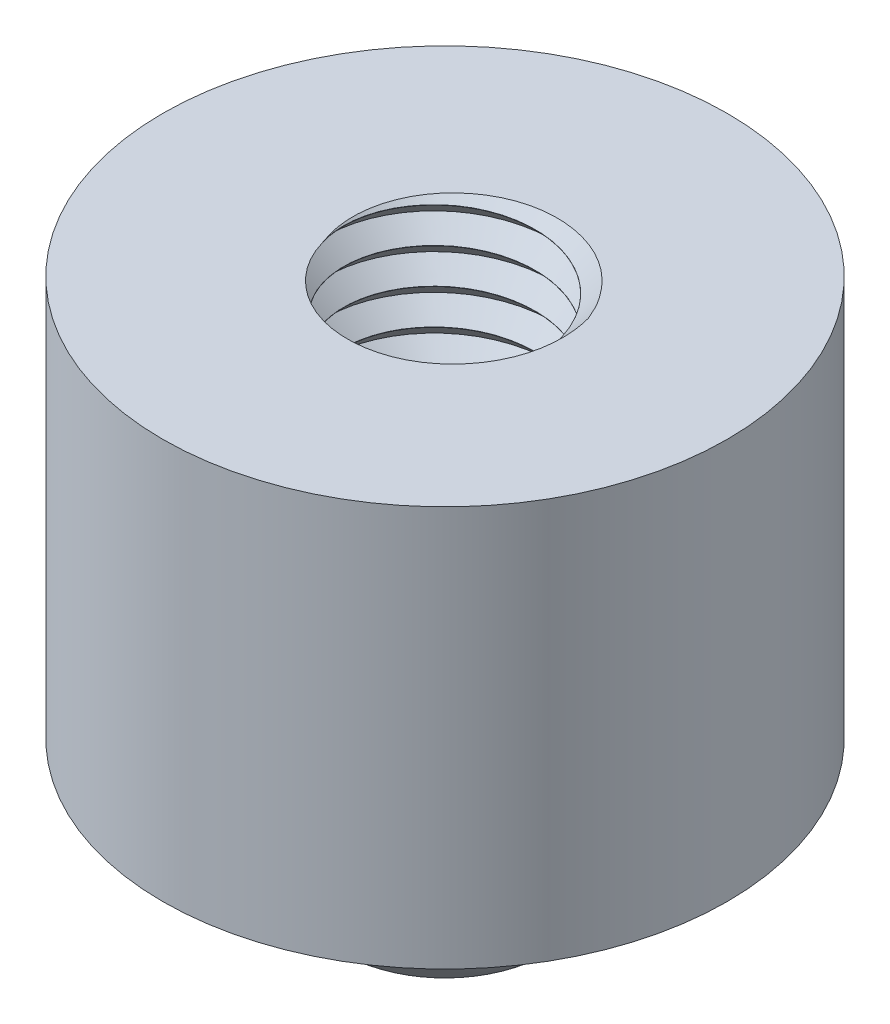
SolidWorks part; units mm, degrees
other "Markup1"
sketch "Sketch7" plane through (8, -40.1821, 8) normal (0.788, -0.5726, 0.226) x (0.2068, -0.0996, -0.9733)
other "Markup2"
sketch "Sketch8" plane through (10, -42.1821, -10) normal (0.2153, -0.7341, -0.6439) x (-0.8854, 0.1314, -0.4459)
material "7075-T6，板材(SS)"
ref_plane "前视基准面" through (0, 0, 0) normal (0, 0, 1) x (1, 0, 0)
ref_plane "上视基准面" through (0, 0, 0) normal (0, 1, 0) x (1, 0, 0)
ref_plane "右视基准面" through (0, 0, 0) normal (1, 0, 0) x (0, 0, -1)
sketch "草图1" plane through (0, 0, 0) normal (0, 0, 1) x (1, 0, 0)
  line L0 (0, 16.878) -> (0, -16.878) construction
  line L1 (0, 0) -> (3.4, 0) construction
  line L3 (3.4, 0) -> (10, 0)
  line L4 (3.4, 0) -> (3.4, -11)
  line L5 (3.4, -11) -> (10, -11)
  line L6 (10, 0) -> (10, -11)
  point P4 (0, 0)
  dimension "D1" = 3.4
  dimension "D2" = 10
  dimension "D3" = 11
revolve "旋转1" add sketch "草图1" angle 360 about L0
sketch "草图2" plane through (0, -11, 0) normal (0, -1, 0) x (1, 0, 0)
  circle A0 centre (0, 0) radius 3.4 construction
  circle A1 centre (0, 0) radius 3.4
curve "螺旋线/涡状线1" pitch 1.25 height 12.8125 radius 3.4 centre (0, -11, 0) axis (0, 1, 0) start towards (0, 0, -1)
sketch "草图3" plane through (0, 0, 0) normal (1, 0, 0) x (0, 0, -1)
  line L0 (3.4, -11.62) -> (3.4, -10.38)
  line L1 (3.4, -10.38) -> (4.025, -11)
  line L2 (-10, -11) -> (10, -11) construction
  line L3 (0, 0) -> (0, -13.2999) construction
  line L4 (-10, -11) -> (10, -11) construction
  line L5 (3.4, -11.62) -> (4.025, -11)
  spline S0 degree 3 poles (-1995.5188, 50.9214) (-241.4894, -14.1354) (17.2925, -12.3735) (2.4668, -10.8438) (1.335, -10.7656) (0, -10.6875) (-1.335, -10.6094) (-2.4668, -10.5313) (-3.223, -10.4531) (-3.4885, -10.375) (-3.223, -10.2969) (-2.4668, -10.2188) (-0.9577, -10.1146) (0.9577, -10.0104) (2.4668, -9.9063) (3.223, -9.8281) (3.4885, -9.75) (3.223, -9.6719) (2.4668, -9.5938) (0.9577, -9.4896) (-0.9577, -9.3854) (-2.4668, -9.2812) (-3.223, -9.2031) (-3.4885, -9.125) (-3.223, -9.0469) (-2.4668, -8.9687) (-0.9577, -8.8646) (0.9577, -8.7604) (2.4668, -8.6562) (3.223, -8.5781) (3.4885, -8.5) (3.223, -8.4219) (2.4668, -8.3437) (0.9577, -8.2396) (-0.9577, -8.1354) (-2.4668, -8.0312) (-3.223, -7.9531) (-3.4885, -7.875) (-3.223, -7.7969) (-2.4668, -7.7187) (-0.9577, -7.6146) (0.9577, -7.5104) (2.4668, -7.4062) (3.223, -7.3281) (3.4885, -7.25) (3.223, -7.1719) (2.4668, -7.0937) (0.9577, -6.9896) (-0.9577, -6.8854) (-2.4668, -6.7812) (-3.223, -6.7031) (-3.4885, -6.625) (-3.223, -6.5469) (-2.4668, -6.4687) (-0.9577, -6.3646) (0.9577, -6.2604) (2.4668, -6.1562) (3.223, -6.0781) (3.4885, -6) (3.223, -5.9219) (2.4668, -5.8437) (0.9577, -5.7396) (-0.9577, -5.6354) (-2.4668, -5.5312) (-3.223, -5.4531) (-3.4885, -5.375) (-3.223, -5.2969) (-2.4668, -5.2187) (-0.9577, -5.1146) (0.9577, -5.0104) (2.4668, -4.9062) (3.223, -4.8281) (3.4885, -4.75) (3.223, -4.6719) (2.4668, -4.5937) (0.9577, -4.4896) (-0.9577, -4.3854) (-2.4668, -4.2812) (-3.223, -4.2031) (-3.4885, -4.125) (-3.223, -4.0469) (-2.4668, -3.9687) (-0.9577, -3.8646) (0.9577, -3.7604) (2.4668, -3.6562) (3.223, -3.5781) (3.4885, -3.5) (3.223, -3.4219) (2.4668, -3.3437) (0.9577, -3.2396) (-0.9577, -3.1354) (-2.4668, -3.0312) (-3.223, -2.9531) (-3.4885, -2.875) (-3.223, -2.7969) (-2.4668, -2.7187) (-0.9577, -2.6146) (0.9577, -2.5104) (2.4668, -2.4062) (3.223, -2.3281) (3.4885, -2.25) (3.223, -2.1719) (2.4668, -2.0937) (0.9577, -1.9896) (-0.9577, -1.8854) (-2.4668, -1.7812) (-3.223, -1.7031) (-3.4885, -1.625) (-3.223, -1.5469) (-2.4668, -1.4687) (-0.9577, -1.3646) (0.9577, -1.2604) (2.4668, -1.1562) (3.223, -1.0781) (3.4885, -1) (3.223, -0.9219) (2.4668, -0.8437) (0.9577, -0.7396) (-0.9577, -0.6354) (-2.4668, -0.5312) (-3.223, -0.4531) (-3.4885, -0.375) (-3.223, -0.2969) (-2.4668, -0.2187) (-0.9577, -0.1146) (0.9577, -0.0104) (2.4668, 0.0938) (3.223, 0.1719) (3.4885, 0.25) (3.223, 0.3281) (2.4668, 0.4063) (0.9577, 0.5104) (-0.9577, 0.6146) (-2.4668, 0.7188) (-3.223, 0.7969) (-3.4885, 0.875) (-3.223, 0.9531) (-2.4668, 1.0313) (-0.9577, 1.1354) (0.9577, 1.2396) (2.4668, 1.3438) (3.223, 1.4219) (3.4885, 1.5) (3.2231, 1.5781) (2.4664, 1.6563) (-12.6096, 2.6972) (-80.8528, 3.8297) (1999.6627, -15.0448) knots -0.34034 -0.34034 -0.34034 -0.34034 0.006098 0.012195 0.018293 0.02439 0.030488 0.036585 0.042683 0.04878 0.054878 0.060976 0.067073 0.079268 0.085366 0.091463 0.097561 0.103659 0.109756 0.115854 0.128049 0.134146 0.140244 0.146341 0.152439 0.158537 0.164634 0.176829 0.182927 0.189024 0.195122 0.20122 0.207317 0.213415 0.22561 0.231707 0.237805 0.243902 0.25 0.256098 0.262195 0.27439 0.280488 0.286585 0.292683 0.29878 0.304878 0.310976 0.323171 0.329268 0.335366 0.341463 0.347561 0.353659 0.359756 0.371951 0.378049 0.384146 0.390244 0.396341 0.402439 0.408537 0.420732 0.426829 0.432927 0.439024 0.445122 0.45122 0.457317 0.469512 0.47561 0.481707 0.487805 0.493902 0.5 0.506098 0.518293 0.52439 0.530488 0.536585 0.542683 0.54878 0.554878 0.567073 0.573171 0.579268 0.585366 0.591463 0.597561 0.603659 0.615854 0.621951 0.628049 0.634146 0.640244 0.646341 0.652439 0.664634 0.670732 0.676829 0.682927 0.689024 0.695122 0.70122 0.713415 0.719512 0.72561 0.731707 0.737805 0.743902 0.75 0.762195 0.768293 0.77439 0.780488 0.786585 0.792683 0.79878 0.810976 0.817073 0.823171 0.829268 0.835366 0.841463 0.847561 0.859756 0.865854 0.871951 0.878049 0.884146 0.890244 0.896341 0.908537 0.914634 0.920732 0.926829 0.932927 0.939024 0.945122 0.957317 0.963415 0.969512 0.97561 0.981707 0.987805 0.993902 1.225736 1.225736 1.225736 1.225736 only from (3.4, -11) to (0, 1.8125) construction
  spline S1 degree 3 poles (3.4, -11) (3.4, -10.9741) (3.223, -10.9218) (2.4668, -10.8438) (1.335, -10.7656) (0, -10.6875) (-1.335, -10.6094) (-2.4668, -10.5313) (-3.223, -10.4531) (-3.4885, -10.375) (-3.223, -10.2969) (-2.4668, -10.2188) (-0.9577, -10.1146) (0.9577, -10.0104) (2.4668, -9.9063) (3.223, -9.8281) (3.4885, -9.75) (3.223, -9.6719) (2.4668, -9.5938) (0.9577, -9.4896) (-0.9577, -9.3854) (-2.4668, -9.2812) (-3.223, -9.2031) (-3.4885, -9.125) (-3.223, -9.0469) (-2.4668, -8.9687) (-0.9577, -8.8646) (0.9577, -8.7604) (2.4668, -8.6562) (3.223, -8.5781) (3.4885, -8.5) (3.223, -8.4219) (2.4668, -8.3437) (0.9577, -8.2396) (-0.9577, -8.1354) (-2.4668, -8.0312) (-3.223, -7.9531) (-3.4885, -7.875) (-3.223, -7.7969) (-2.4668, -7.7187) (-0.9577, -7.6146) (0.9577, -7.5104) (2.4668, -7.4062) (3.223, -7.3281) (3.4885, -7.25) (3.223, -7.1719) (2.4668, -7.0937) (0.9577, -6.9896) (-0.9577, -6.8854) (-2.4668, -6.7812) (-3.223, -6.7031) (-3.4885, -6.625) (-3.223, -6.5469) (-2.4668, -6.4687) (-0.9577, -6.3646) (0.9577, -6.2604) (2.4668, -6.1562) (3.223, -6.0781) (3.4885, -6) (3.223, -5.9219) (2.4668, -5.8437) (0.9577, -5.7396) (-0.9577, -5.6354) (-2.4668, -5.5312) (-3.223, -5.4531) (-3.4885, -5.375) (-3.223, -5.2969) (-2.4668, -5.2187) (-0.9577, -5.1146) (0.9577, -5.0104) (2.4668, -4.9062) (3.223, -4.8281) (3.4885, -4.75) (3.223, -4.6719) (2.4668, -4.5937) (0.9577, -4.4896) (-0.9577, -4.3854) (-2.4668, -4.2812) (-3.223, -4.2031) (-3.4885, -4.125) (-3.223, -4.0469) (-2.4668, -3.9687) (-0.9577, -3.8646) (0.9577, -3.7604) (2.4668, -3.6562) (3.223, -3.5781) (3.4885, -3.5) (3.223, -3.4219) (2.4668, -3.3437) (0.9577, -3.2396) (-0.9577, -3.1354) (-2.4668, -3.0312) (-3.223, -2.9531) (-3.4885, -2.875) (-3.223, -2.7969) (-2.4668, -2.7187) (-0.9577, -2.6146) (0.9577, -2.5104) (2.4668, -2.4062) (3.223, -2.3281) (3.4885, -2.25) (3.223, -2.1719) (2.4668, -2.0937) (0.9577, -1.9896) (-0.9577, -1.8854) (-2.4668, -1.7812) (-3.223, -1.7031) (-3.4885, -1.625) (-3.223, -1.5469) (-2.4668, -1.4687) (-0.9577, -1.3646) (0.9577, -1.2604) (2.4668, -1.1562) (3.223, -1.0781) (3.4885, -1) (3.223, -0.9219) (2.4668, -0.8437) (0.9577, -0.7396) (-0.9577, -0.6354) (-2.4668, -0.5312) (-3.223, -0.4531) (-3.4885, -0.375) (-3.223, -0.2969) (-2.4668, -0.2187) (-0.9577, -0.1146) (0.9577, -0.0104) (2.4668, 0.0938) (3.223, 0.1719) (3.4885, 0.25) (3.223, 0.3281) (2.4668, 0.4063) (0.9577, 0.5104) (-0.9577, 0.6146) (-2.4668, 0.7188) (-3.223, 0.7969) (-3.4885, 0.875) (-3.223, 0.9531) (-2.4668, 1.0313) (-0.9577, 1.1354) (0.9577, 1.2396) (2.4668, 1.3438) (3.223, 1.4219) (3.4885, 1.5) (3.2231, 1.5781) (2.4664, 1.6563) (1.3363, 1.7343) (0.4422, 1.7866) (0, 1.8125) knots 0 0 0 0 0.006098 0.012195 0.018293 0.02439 0.030488 0.036585 0.042683 0.04878 0.054878 0.060976 0.067073 0.079268 0.085366 0.091463 0.097561 0.103659 0.109756 0.115854 0.128049 0.134146 0.140244 0.146341 0.152439 0.158537 0.164634 0.176829 0.182927 0.189024 0.195122 0.20122 0.207317 0.213415 0.22561 0.231707 0.237805 0.243902 0.25 0.256098 0.262195 0.27439 0.280488 0.286585 0.292683 0.29878 0.304878 0.310976 0.323171 0.329268 0.335366 0.341463 0.347561 0.353659 0.359756 0.371951 0.378049 0.384146 0.390244 0.396341 0.402439 0.408537 0.420732 0.426829 0.432927 0.439024 0.445122 0.45122 0.457317 0.469512 0.47561 0.481707 0.487805 0.493902 0.5 0.506098 0.518293 0.52439 0.530488 0.536585 0.542683 0.54878 0.554878 0.567073 0.573171 0.579268 0.585366 0.591463 0.597561 0.603659 0.615854 0.621951 0.628049 0.634146 0.640244 0.646341 0.652439 0.664634 0.670732 0.676829 0.682927 0.689024 0.695122 0.70122 0.713415 0.719512 0.72561 0.731707 0.737805 0.743902 0.75 0.762195 0.768293 0.77439 0.780488 0.786585 0.792683 0.79878 0.810976 0.817073 0.823171 0.829268 0.835366 0.841463 0.847561 0.859756 0.865854 0.871951 0.878049 0.884146 0.890244 0.896341 0.908537 0.914634 0.920732 0.926829 0.932927 0.939024 0.945122 0.957317 0.963415 0.969512 0.97561 0.981707 0.987805 0.993902 1 1 1 1 construction
  dimension "D1" = 4.025
  dimension "D2" = 0.62
sweep "切除-扫描1" cut profiles "草图3" path "螺旋线/涡状线1" align with end faces yes
sketch "草图4" plane through (0, 0, 0) normal (0, 0, 1) x (1, 0, 0)
  line L0 (-10, -11) -> (10, -11) construction
  line L1 (-10, -11) -> (10, -11) construction
  line L2 (0, 0) -> (0, -14.1821) construction
  line L3 (0, -13.3238) -> (4.025, -11)
  line L4 (4.025, -11) -> (10, -11)
  line L10 (0, -13.3238) -> (0, -14.1821)
  line L14 (10, -11) -> (10, -14.1821)
  line L15 (10, -14.1821) -> (0, -14.1821)
  dimension "D1" = 4.025
  dimension "D2" = 60
revolve "旋转2" add sketch "草图4" angle 360 about L2
sketch "草图9" plane through (0, 0, 0) normal (1, 0, 0) x (0, 0, -1)
  line L0 (-10, -14.1821) -> (10, -14.1821) construction
  line L1 (6, -14.1821) -> (0, -14.1821)
  line L2 (0, -14.1821) -> (0, -20.1821)
  arc A0 (6, -14.1821) -> (0, -20.1821) centre (0, -14.1821) cw
revolve "旋转3" add sketch "草图9" angle 360 about L2
